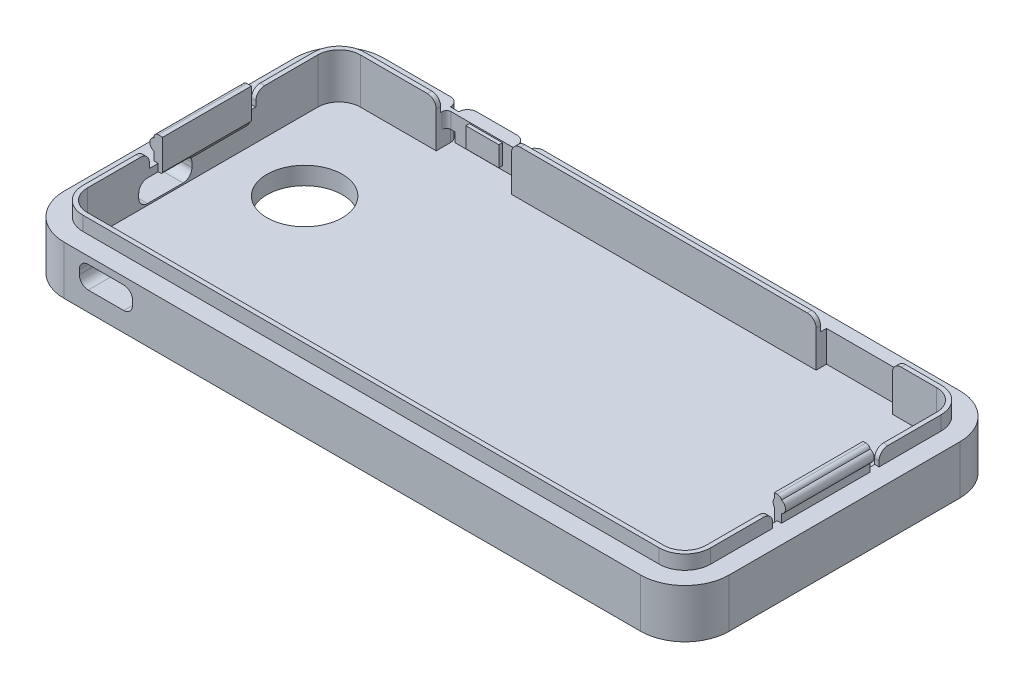
SolidWorks part; units mm, degrees
ref_plane "前视基准面" through (0, 0, 0) normal (0, 0, 1) x (1, 0, 0)
ref_plane "上视基准面" through (0, 0, 0) normal (0, 1, 0) x (1, 0, 0)
ref_plane "右视基准面" through (0, 0, 0) normal (1, 0, 0) x (0, 0, -1)
sketch "zero" plane through (0, 0, 0) normal (0, 1, 0) x (1, 0, 0)
  line L1 (-29.5, 15) -> (29.5, 15)
  line L2 (-32.5, 12) -> (-32.5, -12)
  line L3 (-29.5, -15) -> (29.5, -15)
  line L4 (32.5, 12) -> (32.5, -12)
  line L5 (-32.5, 15) -> (32.5, -15) construction
  line L6 (-32.5, -15) -> (32.5, 15) construction
  line L7 (-25.7, -15) -> (-14.5, -15)
  line L8 (-25.7, -15) -> (-25.7, -9.6569)
  line L9 (-25.7, -9.6569) -> (-14.5, -9.6569)
  line L10 (-14.5, -15) -> (-14.5, -9.6569)
  line L11 (5.2, -15) -> (12.7, -15)
  line L12 (5.2, -15) -> (5.2, -11)
  line L13 (5.2, -11) -> (12.7, -11)
  line L14 (12.7, -15) -> (12.7, -11)
  line L15 (17.8, -15) -> (25.3, -15)
  line L16 (17.8, -15) -> (17.8, -11)
  line L17 (17.8, -11) -> (25.3, -11)
  line L18 (25.3, -15) -> (25.3, -11)
  line L19 (-32.5, 7.7) -> (-19.5, 7.7)
  line L20 (-32.5, 7.7) -> (-32.5, -4.3)
  line L21 (-32.5, -4.3) -> (-19.5, -4.3)
  line L22 (-19.5, 7.7) -> (-19.5, -4.3)
  line L23 (-25.5, 14) -> (25.5, 14)
  line L24 (-25.5, 14) -> (-25.5, 8.8)
  line L25 (-25.5, 8.8) -> (25.5, 8.8)
  line L26 (25.5, 14) -> (25.5, 8.8)
  line L27 (-19.5, 7.2329) -> (-35.5, 7.2329)
  line L28 (-19.5, 7.2329) -> (-19.5, -3.7671)
  line L29 (-19.5, -3.7671) -> (-35.5, -3.7671)
  line L30 (-35.5, 7.2329) -> (-35.5, -3.7671)
  arc A0 (29.5, -15) -> (32.5, -12) centre (29.5, -12) ccw
  arc A1 (29.5, 15) -> (32.5, 12) centre (29.5, 12) cw
  arc A2 (-32.5, -12) -> (-29.5, -15) centre (-29.5, -12) ccw
  arc A3 (-29.5, 15) -> (-32.5, 12) centre (-29.5, 12) ccw
  circle A4 centre (-29, 11.4) radius 3
  circle A5 centre (-29, -11.5) radius 3
  circle A6 centre (29, 11.4) radius 3
  circle A7 centre (29, -11.5) radius 3
  circle A8 centre (-29, 11.4) radius 1.375
  circle A9 centre (-29, -11.5) radius 1.375
  circle A10 centre (29, -11.5) radius 1.375
  circle A11 centre (29, 11.4) radius 1.375
  point P0 (0, 0)
  dimension "D3" = 3
  dimension "D4" = 6
  dimension "D9" = 2.75
  dimension "D1" = 65
  dimension "D2" = 30
  dimension "D5" = 3.6
  dimension "D6" = 3.5
  dimension "D7" = 3.5
  dimension "D8" = 3.5
  dimension "D10" = 12
  dimension "D11" = 7.3
  dimension "D12" = 13
  dimension "D13" = 11.2
  dimension "D14" = 6.8
  dimension "D15" = 19.7
  dimension "D16" = 7.5
  dimension "D17" = 7.5
  dimension "D18" = 5.1
  dimension "D19" = 4
  dimension "D20" = 5.2
  dimension "D21" = 7
  dimension "D22" = 7
  dimension "D23" = 1
  dimension "D24" = 11
  dimension "D25" = 16
sketch "sugar" plane through (0, 0, 0) normal (0, 1, 0) x (1, 0, 0)
  line L1 (-29.5, 15) -> (29.5, 15)
  line L2 (-32.5, 12) -> (-32.5, -12)
  line L3 (-29.5, -15) -> (29.5, -15)
  line L4 (32.5, 12) -> (32.5, -12)
  line L5 (-32.5, 15) -> (32.5, -15) construction
  line L6 (-32.5, -15) -> (32.5, 15) construction
  line L7 (23.5, -11.5) -> (19.5, -11.5)
  line L8 (23.5, -11.5) -> (23.5, -13.9082)
  line L9 (23.5, -13.9082) -> (19.5, -13.9082)
  line L10 (19.5, -11.5) -> (19.5, -13.9082)
  line L11 (16, -11.0071) -> (8.5, -11.0071)
  line L12 (16, -11.0071) -> (16, -15)
  line L13 (16, -15) -> (8.5, -15)
  line L14 (8.5, -11.0071) -> (8.5, -15)
  line L15 (20.5, -13.9082) -> (22.5, -13.9082)
  line L16 (20.5, -13.9082) -> (20.5, -14.8173)
  line L17 (20.5, -14.8173) -> (22.5, -14.8173)
  line L18 (22.5, -13.9082) -> (22.5, -14.8173)
  arc A0 (29.5, 15) -> (32.5, 12) centre (29.5, 12) cw
  arc A1 (29.5, -15) -> (32.5, -12) centre (29.5, -12) ccw
  arc A2 (-32.5, -12) -> (-29.5, -15) centre (-29.5, -12) ccw
  arc A3 (-29.5, 15) -> (-32.5, 12) centre (-29.5, 12) ccw
  circle A4 centre (-29, 11.4) radius 3
  circle A5 centre (-29, 11.4) radius 1.375
  circle A6 centre (-29, -11.5) radius 3
  circle A7 centre (-29, -11.5) radius 1.375
  circle A8 centre (29, 11.4) radius 3
  circle A9 centre (29, 11.4) radius 1.375
  circle A10 centre (29, -11.5) radius 3
  circle A11 centre (29, -11.5) radius 1.375
  dimension "D3" = 3
  dimension "D1" = 65
  dimension "D2" = 30
  dimension "D4" = 9
  dimension "D5" = 4
  dimension "D6" = 3.5
  dimension "D7" = 7.5
  dimension "D8" = 2
  dimension "D9" = 1
sketch "case" plane through (0, 0, 0) normal (0, 1, 0) x (1, 0, 0)
  line L1 (-34.0422, 18) -> (30.9578, 18)
  line L2 (-39.0422, 13) -> (-39.0422, -13)
  line L3 (-34.0422, -18) -> (30.9578, -18)
  line L4 (35.9578, 13) -> (35.9578, -13)
  line L5 (-39.0422, 18) -> (35.9578, -18) construction
  line L6 (-39.0422, -18) -> (35.9578, 18) construction
  arc A0 (-39.0422, -13) -> (-34.0422, -18) centre (-34.0422, -13) ccw
  arc A1 (30.9578, -18) -> (35.9578, -13) centre (30.9578, -13) ccw
  arc A2 (30.9578, 18) -> (35.9578, 13) centre (30.9578, 13) cw
  arc A3 (-34.0422, 18) -> (-39.0422, 13) centre (-34.0422, 13) ccw
  point P0 (-1.5422, 0)
  point P3 (-1.5422, 0)
  dimension "D3" = 5
  dimension "D1" = 75
  dimension "D2" = 36
extrude "凸台-拉伸2" add sketch "case" along normal blind 5.5
sketch "草图2" plane through (0, 0, 0) normal (0, 1, 0) x (1, 0, 0)
  line L4 (-34.0422, -15.4) -> (30.9578, -15.4)
  line L5 (33.3578, -13) -> (33.3578, 13)
  line L6 (30.9578, 15.4) -> (-34.0422, 15.4)
  line L7 (-36.4422, 13) -> (-36.4422, -13)
  line L8 (33.8578, -13) -> (33.8578, 13)
  line L9 (30.9578, 15.9) -> (-34.0422, 15.9)
  line L10 (-36.9422, 13) -> (-36.9422, -13)
  line L11 (-34.0422, -15.9) -> (30.9578, -15.9)
  line L12 (33.8578, -13) -> (33.8578, 13)
  line L13 (30.9578, 15.9) -> (-34.0422, 15.9)
  line L14 (-36.9422, 13) -> (-36.9422, -13)
  line L15 (-34.0422, -15.9) -> (30.9578, -15.9)
  arc A4 (30.9578, -15.4) -> (33.3578, -13) centre (30.9578, -13) ccw
  arc A5 (33.3578, 13) -> (30.9578, 15.4) centre (30.9578, 13) ccw
  arc A6 (-34.0422, 15.4) -> (-36.4422, 13) centre (-34.0422, 13) ccw
  arc A7 (-36.4422, -13) -> (-34.0422, -15.4) centre (-34.0422, -13) ccw
  arc A8 (30.9578, -15.9) -> (33.8578, -13) centre (30.9578, -13) ccw
  arc A9 (33.8578, 13) -> (30.9578, 15.9) centre (30.9578, 13) ccw
  arc A10 (-34.0422, 15.9) -> (-36.9422, 13) centre (-34.0422, 13) ccw
  arc A11 (-36.9422, -13) -> (-34.0422, -15.9) centre (-34.0422, -13) ccw
  arc A12 (30.9578, -15.9) -> (33.8578, -13) centre (30.9578, -13) ccw
  arc A13 (33.8578, 13) -> (30.9578, 15.9) centre (30.9578, 13) ccw
  arc A14 (-34.0422, 15.9) -> (-36.9422, 13) centre (-34.0422, 13) ccw
  arc A15 (-36.9422, -13) -> (-34.0422, -15.9) centre (-34.0422, -13) ccw
  dimension "D1" = 2.1
  dimension "D2" = 0.5
ref_plane "基准面1" through (0, 5.5, 0) normal (0, 1, 0) x (1, 0, 0)
sketch "草图3" plane through (0, 5.5, 0) normal (0, 1, 0) x (1, 0, 0)
  line L4 (-34.0422, -15.4) -> (30.9578, -15.4)
  line L5 (33.3578, -13) -> (33.3578, 13)
  line L6 (30.9578, 15.4) -> (-34.0422, 15.4)
  line L7 (-36.4422, 13) -> (-36.4422, -13)
  line L8 (-34.0422, -15.4) -> (30.9578, -15.4)
  line L9 (33.3578, -13) -> (33.3578, 13)
  line L10 (30.9578, 15.4) -> (-34.0422, 15.4)
  line L11 (-36.4422, 13) -> (-36.4422, -13)
  line L12 (-36.9422, 13) -> (-36.9422, -13)
  line L13 (-34.0422, -15.9) -> (30.9578, -15.9)
  line L14 (33.8578, -13) -> (33.8578, 13)
  line L15 (30.9578, 15.9) -> (-34.0422, 15.9)
  line L16 (-36.9422, 13) -> (-36.9422, -13)
  line L17 (-34.0422, -15.9) -> (30.9578, -15.9)
  line L18 (33.8578, -13) -> (33.8578, 13)
  line L19 (30.9578, 15.9) -> (-34.0422, 15.9)
  arc A4 (30.9578, -15.4) -> (33.3578, -13) centre (30.9578, -13) ccw
  arc A5 (33.3578, 13) -> (30.9578, 15.4) centre (30.9578, 13) ccw
  arc A6 (-34.0422, 15.4) -> (-36.4422, 13) centre (-34.0422, 13) ccw
  arc A7 (-36.4422, -13) -> (-34.0422, -15.4) centre (-34.0422, -13) ccw
  arc A8 (30.9578, -15.4) -> (33.3578, -13) centre (30.9578, -13) ccw
  arc A9 (33.3578, 13) -> (30.9578, 15.4) centre (30.9578, 13) ccw
  arc A10 (-34.0422, 15.4) -> (-36.4422, 13) centre (-34.0422, 13) ccw
  arc A11 (-36.4422, -13) -> (-34.0422, -15.4) centre (-34.0422, -13) ccw
  arc A12 (-36.9422, -13) -> (-34.0422, -15.9) centre (-34.0422, -13) ccw
  arc A13 (30.9578, -15.9) -> (33.8578, -13) centre (30.9578, -13) ccw
  arc A14 (33.8578, 13) -> (30.9578, 15.9) centre (30.9578, 13) ccw
  arc A15 (-34.0422, 15.9) -> (-36.9422, 13) centre (-34.0422, 13) ccw
  arc A16 (-36.9422, -13) -> (-34.0422, -15.9) centre (-34.0422, -13) ccw
  arc A17 (30.9578, -15.9) -> (33.8578, -13) centre (30.9578, -13) ccw
  arc A18 (33.8578, 13) -> (30.9578, 15.9) centre (30.9578, 13) ccw
  arc A19 (-34.0422, 15.9) -> (-36.9422, 13) centre (-34.0422, 13) ccw
  dimension "D1" = 0
  dimension "D2" = 0
extrude "凸台-拉伸4" add sketch "草图3" along normal blind 1.6
sketch "草图5" plane through (0, 5.5, 0) normal (0, 1, 0) x (1, 0, 0)
  line L0 (33.3578, -13) -> (33.3578, 13) construction
  line L1 (33.0578, 5) -> (33.3578, 5)
  line L2 (33.0578, 5) -> (33.0578, -5)
  line L3 (33.0578, -5) -> (33.3578, -5)
  line L4 (33.3578, 5) -> (33.3578, -5)
  line L5 (33.0578, 5) -> (33.3578, -5) construction
  line L6 (33.0578, -5) -> (33.3578, 5) construction
  point P0 (33.2078, 0)
  dimension "D2" = 10
  dimension "D3" = 0.3
  dimension "D4" = 0
ref_plane "基准面3" through (33.8578, 0, 0) normal (1, 0, 0) x (0, 0, -1)
sketch "草图7" plane through (0, 5.5, 0) normal (0, 1, 0) x (1, 0, 0)
  line L0 (-36.9422, 13) -> (-36.9422, -13) construction
  line L1 (-36.9422, 5) -> (-36.4422, 5)
  line L2 (-36.9422, 5) -> (-36.9422, -5)
  line L3 (-36.9422, -5) -> (-36.4422, -5)
  line L4 (-36.4422, 5) -> (-36.4422, -5)
  line L5 (-36.4422, 13) -> (-36.4422, -13) construction
  point P10 (-36.4422, 0)
  dimension "D1" = 5
  dimension "D2" = 10
extrude "凸台-拉伸8" add sketch "草图7" along normal blind 2.8
ref_plane "基准面5" through (0, 0, 5) normal (0, 0, 1) x (1, 0, 0)
sketch "草图8" plane through (0, 0, 5) normal (0, 0, 1) x (1, 0, 0)
  line L0 (-34.0422, 5.5) -> (-39.0422, 5.5) construction
  line L1 (-36.9422, 8.3) -> (-36.9422, 7.1) construction
  circle A0 centre (-36.6922, 7.1) radius 0.7
  dimension "D1" = 1.4
  dimension "D2" = 1.6
  dimension "D3" = 0.25
extrude "凸台-拉伸9" add sketch "草图8" against normal blind 10
fillet "圆角1" radius 0.5 1 edges at (-36.9422, 8.3, 0)
ref_plane "基准面7" through (-36.9422, 0, 0) normal (-1, 0, 0) x (0, 0, 1)
sketch "草图11" plane through (-36.9422, 0, 0) normal (-1, 0, 0) x (0, 0, 1)
  line L0 (-13, 5.5) -> (13, 5.5) construction
  line L1 (5, 7.1) -> (6, 7.1)
  line L2 (5, 7.1) -> (5, 5.5)
  line L3 (5, 5.5) -> (6, 5.5)
  line L4 (6, 7.1) -> (6, 5.5)
  line L6 (-5, 7.1) -> (-6, 7.1)
  line L7 (-5, 7.1) -> (-5, 5.5)
  line L8 (-5, 5.5) -> (-6, 5.5)
  line L9 (-6, 7.1) -> (-6, 5.5)
  dimension "D1" = 1
  dimension "D2" = 1
extrude "切除-拉伸1" cut sketch "草图11" against normal blind 1.2
fillet "圆角2" radius 1 2 edges at (-36.6922, 7.1, 6) (-36.6922, 7.1, -6)
sketch "草图13" plane through (0, 5.5, 0) normal (0, 1, 0) x (1, 0, 0)
  line L1 (-36.4422, -5) -> (-35.9422, -5)
  line L2 (-36.4422, -5) -> (-36.4422, 5)
  line L3 (-36.4422, 5) -> (-35.9422, 5)
  line L4 (-35.9422, -5) -> (-35.9422, 5)
  dimension "D1" = 0.5
extrude "凸台-拉伸10" add sketch "草图13" along normal blind 2.8
sketch "草图14" plane through (0, 5.5, 0) normal (0, 1, 0) x (1, 0, 0)
  line L4 (-34.0422, -15.4) -> (30.9578, -15.4)
  line L5 (33.3578, -13) -> (33.3578, 13)
  line L6 (30.9578, 15.4) -> (-34.0422, 15.4)
  line L7 (-36.4422, 13) -> (-36.4422, -13)
  line L8 (-34.0422, -15.4) -> (30.9578, -15.4)
  line L9 (33.3578, -13) -> (33.3578, 13)
  line L10 (30.9578, 15.4) -> (-34.0422, 15.4)
  line L11 (-36.4422, 13) -> (-36.4422, -13)
  arc A4 (30.9578, -15.4) -> (33.3578, -13) centre (30.9578, -13) ccw
  arc A5 (33.3578, 13) -> (30.9578, 15.4) centre (30.9578, 13) ccw
  arc A6 (-34.0422, 15.4) -> (-36.4422, 13) centre (-34.0422, 13) ccw
  arc A7 (-36.4422, -13) -> (-34.0422, -15.4) centre (-34.0422, -13) ccw
  arc A8 (30.9578, -15.4) -> (33.3578, -13) centre (30.9578, -13) ccw
  arc A9 (33.3578, 13) -> (30.9578, 15.4) centre (30.9578, 13) ccw
  arc A10 (-34.0422, 15.4) -> (-36.4422, 13) centre (-34.0422, 13) ccw
  arc A11 (-36.4422, -13) -> (-34.0422, -15.4) centre (-34.0422, -13) ccw
  dimension "D1" = 0
extrude "切除-拉伸2" cut sketch "草图14" against normal blind 3.5
extrude "凸台-拉伸11" add sketch "草图13<2>" against normal blind 2
sketch "草图13<2>" plane through (0, 5.5, 0) normal (0, 1, 0) x (1, 0, 0) same geometry as "草图13"
extrude "凸台-拉伸12" add sketch "草图5" against normal blind 2 and the other way blind 1.6
sketch "草图17" plane through (0, 7.1, 0) normal (0, 1, 0) x (1, 0, 0)
  line L0 (33.3578, -13) -> (33.3578, -5) construction
  line L1 (33.3578, -5) -> (33.8578, -5)
  line L2 (33.3578, -5) -> (33.3578, -6)
  line L3 (33.3578, -6) -> (33.8578, -6)
  line L4 (33.8578, -5) -> (33.8578, -6)
  line L5 (33.3578, -13) -> (33.3578, 13) construction
  line L6 (33.8578, -13) -> (33.8578, 13) construction
  line L8 (33.3578, 5) -> (33.8578, 5)
  line L9 (33.3578, 5) -> (33.3578, 6)
  line L10 (33.3578, 6) -> (33.8578, 6)
  line L11 (33.8578, 5) -> (33.8578, 6)
  dimension "D1" = 1
  dimension "D2" = 1
extrude "切除-拉伸3" cut sketch "草图17" against normal blind 1.6
sketch "草图19" plane through (0, 7.1, 0) normal (0, 1, 0) x (1, 0, 0)
  line L0 (33.0578, 5) -> (33.0578, -5) construction
  line L1 (33.8578, -5) -> (33.0578, -5)
  line L2 (33.8578, -5) -> (33.8578, 5)
  line L3 (33.8578, 5) -> (33.0578, 5)
  line L4 (33.0578, -5) -> (33.0578, 5)
extrude "凸台-拉伸15" add sketch "草图19" along normal blind 1
sketch "草图20" plane through (0, 0, -5) normal (0, 0, -1) x (-1, 0, 0)
  line L0 (-30.9578, 5.5) -> (-35.9578, 5.5) construction
  line L3 (-33.8578, 5.5) -> (-33.8578, 8.1) construction
  circle A0 centre (-33.6078, 7.1) radius 0.7
  dimension "D1" = 1.4
  dimension "D2" = 1.6
  dimension "D3" = 0.25
extrude "凸台-拉伸16" add sketch "草图20" against normal blind 10
fillet "圆角4" radius 0.5 1 edges at (33.8578, 8.1, 0)
sketch "草图33" plane through (0, 2, 0) normal (0, 1, 0) x (1, 0, 0)
  line L3 (-39.0422, 13) -> (-39.0422, -13) construction
  line L4 (30.9578, 18) -> (-34.0422, 18) construction
  circle A0 centre (-28.5006, 3.5706) radius 4.25
  dimension "D1" = 8.5
  dimension "D2" = 10.5416
  dimension "D3" = 14.4294
chamfer "倒角11" distance 1 angle 54 1 edges at (-35.9422, 3.5, 0) first distance on face at (-36.1922, 3.5, 0)
fillet "圆角5" radius 1 2 edges at (33.6078, 7.1, 6) (33.6078, 7.1, -6)
extrude "切除-拉伸17" cut sketch "草图33" against normal up to next
sketch "草图44" plane through (0, 0, 0) normal (0, -1, 0) x (1, 0, 0)
  line B0 (-7.9307, 5.5082) -> (-8.7513, 5.9812)
  line B1 (-8.7513, 5.9812) -> (-13.0081, 8.4374)
  line B2 (-13.0081, 8.4374) -> (-13.8287, 8.9161)
  line B3 (-15.5497, 8.9161) -> (-16.3704, 8.4374)
  line B4 (-16.3704, 8.4374) -> (-20.6272, 5.9812)
  line B5 (-20.6272, 5.9812) -> (-21.4479, 5.5082)
  line B6 (-22.3084, 4.0209) -> (-22.3084, -2.7947)
  line B7 (-21.4479, -4.282) -> (-20.6272, -4.755)
  line B8 (-20.6272, -4.755) -> (-16.3704, -7.2112)
  line B9 (-16.3704, -7.2112) -> (-15.5497, -7.6898)
  line B10 (-13.8287, -7.6898) -> (-13.0081, -7.2112)
  line B11 (-13.0081, -7.2112) -> (-8.7513, -4.755)
  line B12 (-8.7513, -4.755) -> (-7.9307, -4.282)
  line B13 (-7.0702, -2.7947) -> (-7.0702, 4.0209)
  line B14 (-20.3537, 4.8301) -> (-15.0882, 7.8732)
  line B15 (-14.2846, 7.8732) -> (-9.0476, 4.8244)
  line B16 (-9.0419, 4.1235) -> (-14.1308, 1.0804)
  line B17 (-12.5522, -4.0769) -> (-13.1449, -4.4074)
  line B18 (-13.2019, -4.5043) -> (-13.2019, -6.2139)
  line B19 (-13.2588, -6.3108) -> (-14.3644, -6.9376)
  line B20 (-14.5297, -6.8407) -> (-14.5297, -1.5638)
  line B21 (-14.4727, -1.4669) -> (-12.5921, -0.4013)
  line B22 (-8.6487, -3.7236) -> (-9.7428, -4.3447)
  line B23 (-9.9081, -4.2479) -> (-9.9081, -1.7347)
  line B24 (-9.8511, -1.6379) -> (-8.757, -1.0224)
  line B25 (-8.5917, -1.1193) -> (-8.5917, -3.6267)
  line B26 (-12.6207, -3.0625) -> (-13.1449, -3.3247)
  line B27 (-13.2019, -3.205) -> (-13.2019, -1.8601)
  line B28 (-13.1449, -1.7632) -> (-12.6548, -1.4897)
  line B29 (-3.0754, 3.5422) -> (-4.9503, 3.5422)
  line B30 (-4.9503, 3.5422) -> (-4.9503, -3.0226)
  line B31 (-4.9503, -3.0226) -> (-4.1182, -3.0226)
  line B32 (-4.1182, -3.0226) -> (-4.1182, -0.4183)
  line B33 (-4.1182, -0.4183) -> (-3.0298, -0.4183)
  line B34 (-3.138, 0.2541) -> (-4.1182, 0.2541)
  line B35 (-4.1182, 0.2541) -> (-4.1182, 2.8698)
  line B36 (-4.1182, 2.8698) -> (-3.1722, 2.8698)
  line B37 (0.4634, 1.844) -> (0.4634, -3.0226)
  line B38 (0.4634, -3.0226) -> (1.2784, -3.0226)
  line B39 (1.2784, -3.0226) -> (1.2784, 1.844)
  line B40 (1.2784, 1.844) -> (0.4634, 1.844)
  line B41 (5.9855, 0.767) -> (5.1535, 1.0975)
  line B42 (6.3103, 1.8839) -> (7.1081, 2.8869)
  line B43 (3.877, -0.0764) -> (4.7261, -0.4355)
  line B44 (3.176, -1.0851) -> (2.27, -2.1906)
  line B45 (11.0915, 2.072) -> (11.0915, -1.2675)
  line B46 (9.6497, -0.8799) -> (9.6497, 2.072)
  line B47 (9.6497, 2.072) -> (8.0598, 2.072)
  line B48 (8.0598, 2.072) -> (8.0598, -1.0794)
  line B49 (11.2738, -2.3217) -> (11.3878, -3.0226)
  line B50 (11.3878, -3.0226) -> (12.6871, -3.0226)
  line B51 (12.6871, -3.0226) -> (12.6871, 2.072)
  line B52 (12.6871, 2.072) -> (11.0915, 2.072)
  line B53 (16.5394, -2.0197) -> (15.7359, -2.0197)
  line B54 (17.6335, 0.9208) -> (18.4199, 0.9208)
  line B55 (18.4199, 0.9208) -> (18.4199, 2.072)
  line B56 (18.4199, 2.072) -> (16.5508, 2.072)
  line B57 (15.753, -3.2392) -> (16.2374, -3.2392)
  line B58 (18.8758, 1.5306) -> (19.4343, 0.482)
  line B59 (21.6796, -2.5098) -> (21.8334, -3.0226)
  line B60 (21.8334, -3.0226) -> (23.1327, -3.0226)
  line B61 (23.1327, -3.0226) -> (23.1327, -0.1277)
  line B62 (21.5371, -0.6919) -> (21.5371, -1.5068)
  line B63 (25.6231, 1.1887) -> (25.4806, 2.072)
  line B64 (25.4806, 2.072) -> (24.1813, 2.072)
  line B65 (24.1813, 2.072) -> (24.1813, -3.0226)
  line B66 (24.1813, -3.0226) -> (25.7655, -3.0226)
  line B67 (25.7655, -3.0226) -> (25.7655, -0.1106)
  line B68 (27.4238, 0.7214) -> (27.6916, 2.0948)
  line B69 (-13.1449, -3.3247) -> (-13.1449, -4.4074)
  line B70 (-13.2019, -3.205) -> (-13.2019, -4.5043)
  spline B71 degree 3 poles (-13.8287, 8.9161) (-14.0966, 9.0642) (-14.3929, 9.144) (-14.6892, 9.144) knots 3 3 3 3 4 4 4 4
  spline B72 degree 3 poles (-14.6892, 9.144) (-14.9856, 9.144) (-15.2819, 9.0642) (-15.5497, 8.9161) knots 4 4 4 4 5 5 5 5
  spline B73 degree 3 poles (-21.4479, 5.5082) (-21.9778, 5.2005) (-22.3084, 4.6307) (-22.3084, 4.0209) knots 8 8 8 8 9 9 9 9
  spline B74 degree 3 poles (-22.3084, -2.7947) (-22.3084, -3.4101) (-21.9778, -3.9743) (-21.4479, -4.282) knots 10 10 10 10 11 11 11 11
  spline B75 degree 3 poles (-15.5497, -7.6898) (-15.2819, -7.8437) (-14.9856, -7.9178) (-14.6892, -7.9178) knots 14 14 14 14 15 15 15 15
  spline B76 degree 3 poles (-14.6892, -7.9178) (-14.3929, -7.9178) (-14.0966, -7.8437) (-13.8287, -7.6898) knots 15 15 15 15 16 16 16 16
  spline B77 degree 3 poles (-7.9307, -4.282) (-7.395, -3.9743) (-7.0702, -3.4101) (-7.0702, -2.7947) knots 19 19 19 19 20 20 20 20
  spline B78 degree 3 poles (-7.0702, 4.0209) (-7.0702, 4.6307) (-7.395, 5.2005) (-7.9307, 5.5082) knots 21 21 21 21 22 22 22 22
  spline B79 degree 2 poles (-15.242, 1.0804) (-20.3936, 4.0551) (-20.405, 4.0608) knots 0 0 0 1 1 1
  spline B80 degree 3 poles (-20.405, 4.0608) (-20.6728, 4.2545) (-20.6443, 4.6649) (-20.3537, 4.8301) knots 1 1 1 1 2 2 2 2
  spline B81 degree 3 poles (-15.0882, 7.8732) (-14.8431, 8.0157) (-14.5353, 8.0157) (-14.2846, 7.8732) knots 3 3 3 3 4 4 4 4
  spline B82 degree 3 poles (-9.0476, 4.8244) (-8.7798, 4.6706) (-8.7741, 4.2831) (-9.0419, 4.1235) knots 5 5 5 5 6 6 6 6
  spline B83 degree 3 poles (-14.1308, 1.0804) (-14.4727, 0.8809) (-14.9001, 0.8809) (-15.242, 1.0804) knots 7 7 7 7 8 8 8 8
  spline B84 degree 3 poles (-13.2019, -6.2139) (-13.2019, -6.2538) (-13.219, -6.288) (-13.2588, -6.3108) knots 3 3 3 3 4 4 4 4
  spline B85 degree 3 poles (-14.3644, -6.9376) (-14.4385, -6.9775) (-14.5297, -6.9262) (-14.5297, -6.8407) knots 5 5 5 5 6 6 6 6
  spline B86 degree 3 poles (-14.5297, -1.5638) (-14.5297, -1.5239) (-14.5126, -1.484) (-14.4727, -1.4669) knots 7 7 7 7 8 8 8 8
  spline B87 degree 3 poles (-12.5921, -0.4013) (-11.3726, 0.2883) (-10.364, 0.4251) (-10.364, -0.9426) knots 9 9 9 9 10 10 10 10
  spline B88 degree 3 poles (-10.364, -0.9426) (-10.364, -2.259) (-11.384, -3.4158) (-12.5522, -4.0769) knots 10 10 10 10 11 11 11 11
  spline B89 degree 3 poles (-8.5917, -3.6267) (-8.5917, -3.6666) (-8.6145, -3.7065) (-8.6487, -3.7236) knots 0 0 0 0 1 1 1 1
  spline B90 degree 3 poles (-9.7428, -4.3447) (-9.8169, -4.3846) (-9.9081, -4.3333) (-9.9081, -4.2479) knots 2 2 2 2 3 3 3 3
  spline B91 degree 3 poles (-9.9081, -1.7347) (-9.9081, -1.6949) (-9.8853, -1.6606) (-9.8511, -1.6379) knots 4 4 4 4 5 5 5 5
  spline B92 degree 3 poles (-8.757, -1.0224) (-8.6829, -0.9825) (-8.5917, -1.0338) (-8.5917, -1.1193) knots 6 6 6 6 7 7 7 7
  spline B93 degree 3 poles (-9.247, 0.6473) (-8.8082, 0.898) (-8.4948, 0.7898) (-8.4948, 0.3909) (-8.4948, -0.0023) (-8.8082, -0.4639) (-9.247, -0.709) knots 2 2 2 2 3 3 3 4 4 4 4
  spline B94 degree 3 poles (-9.247, -0.709) (-9.6915, -0.9654) (-10.0049, -0.8571) (-10.0049, -0.4639) (-10.0049, -0.0593) (-9.6915, 0.3966) (-9.247, 0.6473) knots 0 0 0 0 1 1 1 2 2 2 2
  spline B95 degree 3 poles (-11.6633, -1.6778) (-11.6633, -2.2191) (-11.9709, -2.6978) (-12.6207, -3.0625) knots 0 0 0 0 1 1 1 1
  spline B96 degree 3 poles (-13.2019, -1.8601) (-13.2019, -1.8202) (-13.1791, -1.7803) (-13.1449, -1.7632) knots 4 4 4 4 5 5 5 5
  spline B97 degree 3 poles (-12.6548, -1.4897) (-12.0166, -1.125) (-11.6633, -1.1193) (-11.6633, -1.6778) knots 6 6 6 6 7 7 7 7
  spline B98 degree 3 poles (-3.0298, -0.4183) (-1.5994, -0.4183) (-0.6136, 0.2313) (-0.6136, 1.6161) knots 5 5 5 5 6 6 6 6
  spline B99 degree 3 poles (-0.6136, 1.6161) (-0.6136, 3.0521) (-1.5994, 3.5422) (-3.0754, 3.5422) knots 6 6 6 6 7 7 7 7
  spline B100 degree 3 poles (-3.1722, 2.8698) (-2.0211, 2.8698) (-1.4398, 2.5678) (-1.4398, 1.6161) knots 3 3 3 3 4 4 4 4
  spline B101 degree 3 poles (-1.4398, 1.6161) (-1.4398, 0.6758) (-1.9813, 0.2541) (-3.138, 0.2541) knots 4 4 4 4 5 5 5 5
  spline B102 degree 3 poles (0.8738, 2.847) (1.1986, 2.847) (1.4379, 3.0692) (1.4379, 3.3712) (1.4379, 3.7075) (1.1986, 3.9012) (0.8738, 3.9012) knots 2 2 2 2 3 3 3 4 4 4 4
  spline B103 degree 3 poles (0.8738, 3.9012) (0.549, 3.9012) (0.3096, 3.7075) (0.3096, 3.3712) (0.3096, 3.0692) (0.549, 2.847) (0.8738, 2.847) knots 0 0 0 0 1 1 1 2 2 2 2
  spline B104 degree 3 poles (5.1535, 1.0975) (4.5665, 1.3312) (4.1448, 1.4736) (4.1448, 1.844) knots 1 1 1 1 2 2 2 2
  spline B105 degree 3 poles (4.1448, 1.844) (4.1448, 2.1973) (4.4469, 2.3968) (4.9426, 2.3968) knots 2 2 2 2 3 3 3 3
  spline B106 degree 3 poles (4.9426, 2.3968) (5.4612, 2.3968) (5.8715, 2.2201) (6.3103, 1.8839) knots 3 3 3 3 4 4 4 4
  spline B107 degree 3 poles (7.1081, 2.8869) (6.5269, 3.4738) (5.7119, 3.7702) (4.9426, 3.7702) knots 5 5 5 5 6 6 6 6
  spline B108 degree 3 poles (4.9426, 3.7702) (3.5237, 3.7702) (2.5207, 2.8698) (2.5207, 1.7528) knots 6 6 6 6 7 7 7 7
  spline B109 degree 3 poles (2.5207, 1.7528) (2.5207, 0.7841) (3.176, 0.2028) (3.877, -0.0764) knots 7 7 7 7 8 8 8 8
  spline B110 degree 3 poles (4.7261, -0.4355) (5.2959, -0.6748) (5.6664, -0.8002) (5.6664, -1.1877) knots 9 9 9 9 10 10 10 10
  spline B111 degree 3 poles (5.6664, -1.1877) (5.6664, -1.5467) (5.3871, -1.7689) (4.7945, -1.7689) knots 10 10 10 10 11 11 11 11
  spline B112 degree 3 poles (4.7945, -1.7689) (4.2702, -1.7689) (3.649, -1.4897) (3.176, -1.0851) knots 11 11 11 11 12 12 12 12
  spline B113 degree 3 poles (2.27, -2.1906) (2.9595, -2.8232) (3.894, -3.148) (4.7602, -3.148) knots 13 13 13 13 14 14 14 14
  spline B114 degree 3 poles (4.7602, -3.148) (6.373, -3.148) (7.3075, -2.1735) (7.3075, -1.0623) knots 14 14 14 14 15 15 15 15
  spline B115 degree 3 poles (7.3075, -1.0623) (7.3075, -0.122) (6.8118, 0.4365) (5.9855, 0.767) knots 15 15 15 15 16 16 16 16
  spline B116 degree 3 poles (11.0915, -1.2675) (10.8237, -1.6436) (10.6014, -1.786) (10.2424, -1.786) knots 1 1 1 1 2 2 2 2
  spline B117 degree 3 poles (10.2424, -1.786) (9.8378, -1.786) (9.6497, -1.5866) (9.6497, -0.8799) knots 2 2 2 2 3 3 3 3
  spline B118 degree 3 poles (8.0598, -1.0794) (8.0749, -2.3501) (8.5574, -3.1422) (9.6685, -3.129) knots 6 6 6 6 7 7 7 7
  spline B119 degree 3 poles (9.6685, -3.129) (10.3637, -3.1373) (10.8462, -2.8182) (11.2738, -2.3217) knots 7 7 7 7 8 8 8 8
  spline B120 degree 3 poles (15.7359, -2.0197) (15.1888, -2.0197) (14.9837, -1.9114) (14.9837, -1.6778) knots 1 1 1 1 2 2 2 2
  spline B121 degree 3 poles (14.9837, -1.6778) (14.9837, -1.5068) (15.0235, -1.427) (15.1432, -1.3187) knots 2 2 2 2 3 3 3 3
  spline B122 degree 3 poles (15.1432, -1.3187) (15.3655, -1.3814) (15.5706, -1.4099) (15.7416, -1.4099) knots 3 3 3 3 4 4 4 4
  spline B123 degree 3 poles (15.7416, -1.4099) (16.8699, -1.4099) (17.776, -0.8913) (17.776, 0.2997) knots 4 4 4 4 5 5 5 5
  spline B124 degree 3 poles (17.776, 0.2997) (17.776, 0.5447) (17.7133, 0.7784) (17.6335, 0.9208) knots 5 5 5 5 6 6 6 6
  spline B125 degree 3 poles (16.5508, 2.072) (16.3171, 2.1574) (16.0379, 2.1973) (15.7416, 2.1973) knots 9 9 9 9 10 10 10 10
  spline B126 degree 3 poles (15.7416, 2.1973) (14.6418, 2.1845) (13.6174, 1.5685) (13.632, 0.3206) knots 10 10 10 10 11 11 11 11
  spline B127 degree 3 poles (13.632, 0.3206) (13.6188, -0.2719) (13.9388, -0.7521) (14.2921, -1.0108) knots 11 11 11 11 12 12 12 12
  spline B128 degree 3 poles (14.2921, -1.0108) (13.9616, -1.2444) (13.7279, -1.6035) (13.7279, -1.9625) knots 13 13 13 13 14 14 14 14
  spline B129 degree 3 poles (13.7279, -1.9625) (13.7279, -2.3899) (13.9274, -2.6577) (14.1952, -2.8401) knots 14 14 14 14 15 15 15 15
  spline B130 degree 3 poles (14.1952, -2.8401) (13.7276, -3.0899) (13.4846, -3.4373) (13.4939, -3.8589) knots 16 16 16 16 17 17 17 17
  spline B131 degree 3 poles (13.4939, -3.8589) (13.4836, -4.7706) (14.4423, -5.152) (15.6162, -5.1653) knots 17 17 17 17 18 18 18 18
  spline B132 degree 3 poles (15.6162, -5.1653) (17.3885, -5.1653) (18.4998, -4.4017) (18.4998, -3.3247) knots 18 18 18 18 19 19 19 19
  spline B133 degree 3 poles (18.4998, -3.3247) (18.4998, -2.4015) (17.7931, -2.0197) (16.5394, -2.0197) knots 19 19 19 19 20 20 20 20
  spline B134 degree 3 poles (15.7416, -0.4525) (15.3769, -0.4525) (15.0977, -0.1847) (15.0977, 0.3453) (15.0977, 0.8639) (15.3769, 1.1317) (15.7416, 1.1317) knots 2 2 2 2 3 3 3 4 4 4 4
  spline B135 degree 3 poles (15.7416, 1.1317) (16.1177, 1.1317) (16.3855, 0.8639) (16.3855, 0.3453) (16.3855, -0.1847) (16.1177, -0.4525) (15.7416, -0.4525) knots 0 0 0 0 1 1 1 2 2 2 2
  spline B136 degree 3 poles (15.8669, -4.1681) (15.2116, -4.1681) (14.7842, -3.9914) (14.7842, -3.6324) knots 0 0 0 0 1 1 1 1
  spline B137 degree 3 poles (14.7842, -3.6324) (14.7842, -3.4614) (14.8639, -3.319) (15.0235, -3.1765) knots 1 1 1 1 2 2 2 2
  spline B138 degree 3 poles (15.0235, -3.1765) (15.1888, -3.2221) (15.3826, -3.2392) (15.753, -3.2392) knots 2 2 2 2 3 3 3 3
  spline B139 degree 3 poles (16.2374, -3.2392) (16.7103, -3.2392) (16.9782, -3.3019) (16.9782, -3.6039) knots 4 4 4 4 5 5 5 5
  spline B140 degree 3 poles (16.9782, -3.6039) (16.9782, -3.9287) (16.5223, -4.1681) (15.8669, -4.1681) knots 5 5 5 5 6 6 6 6
  spline B141 degree 3 poles (21.0699, 2.1973) (20.2777, 2.1973) (19.5483, 1.9295) (18.8758, 1.5306) knots 0 0 0 0 1 1 1 1
  spline B142 degree 3 poles (19.4343, 0.482) (19.9415, 0.767) (20.3632, 0.9265) (20.7678, 0.9265) knots 2 2 2 2 3 3 3 3
  spline B143 degree 3 poles (20.7678, 0.9265) (21.2863, 0.9265) (21.503, 0.6872) (21.5371, 0.2769) knots 3 3 3 3 4 4 4 4
  spline B144 degree 3 poles (21.5371, 0.2769) (19.5483, 0.0603) (18.7048, -0.5209) (18.7048, -1.598) knots 4 4 4 4 5 5 5 5
  spline B145 degree 3 poles (18.7048, -1.598) (18.7048, -2.4471) (19.2804, -3.148) (20.2208, -3.148) knots 5 5 5 5 6 6 6 6
  spline B146 degree 3 poles (20.2208, -3.148) (20.7849, -3.148) (21.2579, -2.8859) (21.6796, -2.5098) knots 6 6 6 6 7 7 7 7
  spline B147 degree 3 poles (23.1327, -0.1277) (23.1327, 1.4679) (22.3862, 2.1973) (21.0699, 2.1973) knots 11 11 11 11 12 12 12 12
  spline B148 degree 3 poles (21.5371, -1.5068) (21.3034, -1.7575) (21.0926, -1.9114) (20.7678, -1.9114) knots 0 0 0 0 1 1 1 1
  spline B149 degree 3 poles (20.7678, -1.9114) (20.4372, -1.9114) (20.2208, -1.7689) (20.2208, -1.4726) knots 1 1 1 1 2 2 2 2
  spline B150 degree 3 poles (20.2208, -1.4726) (20.2208, -1.1136) (20.5456, -0.8287) (21.5371, -0.6919) knots 2 2 2 2 3 3 3 3
  spline B151 degree 3 poles (27.0762, 2.1973) (26.5633, 2.1973) (25.9991, 1.8668) (25.6231, 1.1887) knots 0 0 0 0 1 1 1 1
  spline B152 degree 3 poles (25.7655, -0.1106) (26.0334, 0.5618) (26.4893, 0.8011) (26.8653, 0.8011) knots 7 7 7 7 8 8 8 8
  spline B153 degree 3 poles (26.8653, 0.8011) (27.0933, 0.8011) (27.2415, 0.767) (27.4238, 0.7214) knots 8 8 8 8 9 9 9 9
  spline B154 degree 3 poles (27.6916, 2.0948) (27.5492, 2.1574) (27.3782, 2.1973) (27.0762, 2.1973) knots 10 10 10 10 11 11 11 11
sketch_block_instance "块2-1"
sketch_block "块2"
extrude "切除-拉伸19" cut sketch "草图44" against normal blind 0.5
sketch "草图45" plane through (0, 0, 18) normal (0, 0, 1) x (1, 0, 0)
  line L0 (-39.0422, 0) -> (-34.0422, 0) construction
  line L1 (-26.3406, 2.1843) -> (-32.3406, 2.1843)
  line L2 (-26.3406, 2.1843) -> (-26.3406, 4.6843)
  line L3 (-26.3406, 4.6843) -> (-32.3406, 4.6843)
  line L4 (-32.3406, 2.1843) -> (-32.3406, 4.6843)
  line L5 (-39.0422, 5.5) -> (-39.0422, 0) construction
  dimension "D1" = 6
  dimension "D2" = 2.5
  dimension "D3" = 2.1843
  dimension "D4" = 6.7016
extrude "切除-拉伸20" cut sketch "草图45" against normal up to next
fillet "圆角12" radius 1 4 edges at (-32.3406, 2.1843, 16.7) (-32.3406, 4.6843, 16.7) (-26.3406, 2.1843, 16.7) (-26.3406, 4.6843, 16.7)
sketch "草图46" plane through (0, 7.1, 0) normal (0, 1, 0) x (1, 0, 0)
  line L0 (-39.0422, 13) -> (-39.0422, -13) construction
  line L1 (-25.4906, 15.3706) -> (-16.9906, 15.3706)
  line L2 (-25.4906, 15.3706) -> (-25.4906, 16.5706)
  line L3 (-25.4906, 16.5706) -> (-16.9906, 16.5706)
  line L4 (-16.9906, 15.3706) -> (-16.9906, 16.5706)
  line L5 (35.9578, -13) -> (35.9578, 13) construction
  line L6 (17.3578, 15.3706) -> (25.9578, 15.3706)
  line L7 (17.3578, 15.3706) -> (17.3578, 16.5706)
  line L8 (17.3578, 16.5706) -> (25.9578, 16.5706)
  line L9 (25.9578, 15.3706) -> (25.9578, 16.5706)
  dimension "D1" = 1.2
  dimension "D2" = 8.5
  dimension "D3" = 13.5516
  dimension "D4" = 1.2
  dimension "D5" = 8.6
  dimension "D6" = 10
extrude "切除-拉伸21" cut sketch "草图46" against normal up to surface (5.1 mm away) up to face at (-28.5006, 2, 0.6794)
fillet "圆角13" radius 1 4 edges at (17.3578, 7.1, -15.65) (25.9578, 7.1, -15.65) (-25.4906, 7.1, -15.65) (-16.9906, 7.1, -15.65)
sketch "草图49" plane through (0, 0, -18) normal (0, 0, -1) x (-1, 0, 0)
  line L0 (25.4906, 3.75) -> (24.5368, 3.75)
  line L1 (25.4906, 2) -> (25.4906, 5.5) construction
  line L2 (24.5368, 3.75) -> (24.5368, 2.6843)
  line L3 (24.5368, 2.6843) -> (17.983, 2.6843)
  line L4 (17.983, 2.6843) -> (17.983, 5.5)
  line L5 (-30.9578, 5.5) -> (34.0422, 5.5) construction
  line L6 (17.983, 5.5) -> (16.9906, 5.5)
  line L7 (16.9906, 2) -> (16.9906, 5.5) construction
  line L8 (16.9906, 5.5) -> (16.9906, 2)
  line L9 (25.4906, 2) -> (16.9906, 2) construction
  line L10 (16.9906, 2) -> (25.4906, 2)
  line L11 (25.4906, 2) -> (34.0422, 2) construction
  line L12 (25.4906, 2) -> (25.4906, 3.75)
extrude "切除-拉伸22" cut sketch "草图49" against normal up to next
sketch "草图51" plane through (0, 0, -18) normal (0, 0, -1) x (-1, 0, 0)
  line L0 (17.983, 5.5) -> (34.0422, 5.5) construction
  line L1 (24.5368, 3.75) -> (25.4906, 3.75)
  line L2 (24.5368, 3.75) -> (24.5368, 5.5)
  line L3 (24.5368, 5.5) -> (25.4906, 5.5)
  line L4 (25.4906, 3.75) -> (25.4906, 5.5)
  line L5 (25.4906, 3.75) -> (25.4906, 5.5) construction
extrude "切除-拉伸23" cut sketch "草图51" against normal blind 1
fillet "圆角14" radius 1 4 edges at (-17.983, 4.0922, -18) (-24.5368, 4.0922, -18) (-25.4906, 3.75, -18) (-16.9906, 3.75, -18)
sketch "草图52" plane through (0, 0, -16.5706) normal (0, 0, 1) x (1, 0, 0)
  line L1 (-22.9229, 5.3587) -> (-19.201, 5.3587)
  line L2 (-22.9229, 5.3587) -> (-22.9229, 3.0978)
  line L3 (-22.9229, 3.0978) -> (-19.201, 3.0978)
  line L4 (-19.201, 5.3587) -> (-19.201, 3.0978)
extrude "凸台-拉伸18" add sketch "草图52" along normal blind 0.4
fillet "圆角15" radius 0.5 1 edges at (-25.4906, 4.625, -16.5706)
sketch "草图53" plane through (-39.0422, 0, 0) normal (-1, 0, 0) x (0, 0, 1)
  line L1 (7.2, 2.1843) -> (1.2, 2.1843)
  line L2 (7.2, 2.1843) -> (7.2, 4.6843)
  line L3 (7.2, 4.6843) -> (1.2, 4.6843)
  line L4 (1.2, 2.1843) -> (1.2, 4.6843)
  line L5 (18, 5.5) -> (18, 0) construction
  dimension "D1" = 6
  dimension "D3" = 10.8
extrude "切除-拉伸24" cut sketch "草图53" against normal up to next
fillet "圆角16" radius 1 4 edges at (-37.7422, 4.6843, 7.2) (-37.562, 4.6843, 1.2) (-37.7422, 2.1843, 1.2) (-37.7422, 2.1843, 7.2)
